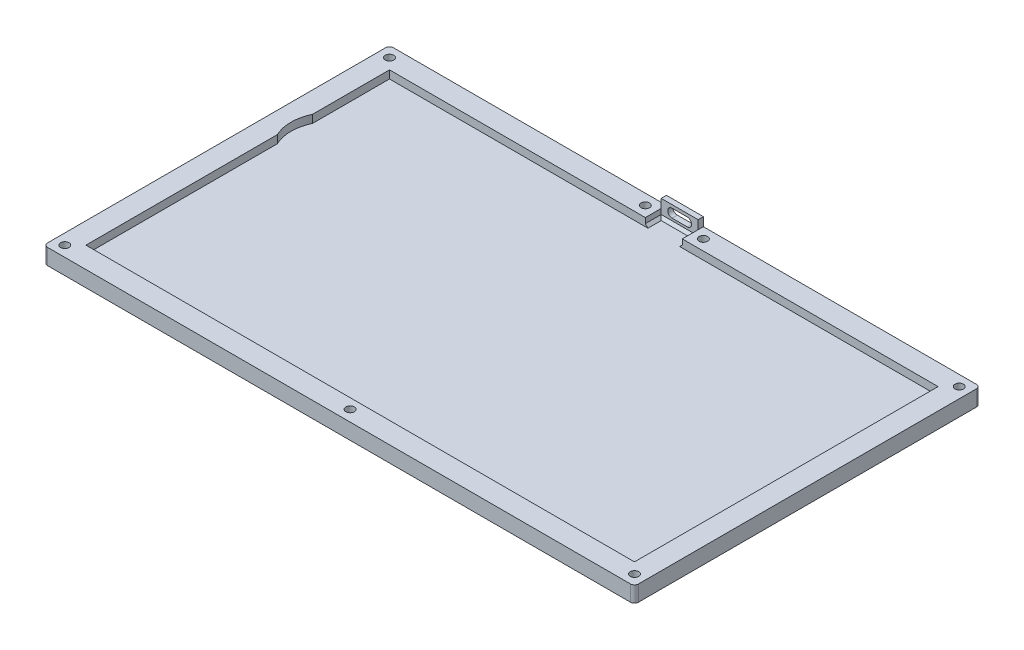
SolidWorks part; units mm, degrees
ref_plane "Front Plane" through (0, 0, 0) normal (0, 0, 1) x (1, 0, 0)
ref_plane "Top Plane" through (0, 0, 0) normal (0, 1, 0) x (1, 0, 0)
ref_plane "Right Plane" through (0, 0, 0) normal (1, 0, 0) x (0, 0, -1)
sketch "Sketch1" plane through (0, 0, 0) normal (0, 1, 0) x (1, 0, 0)
  line L1 (6.4113, 22.7059) -> (230.2097, 22.7059)
  line L2 (6.4113, 22.7059) -> (6.4113, 153.7054)
  line L3 (6.4113, 153.7054) -> (230.2097, 153.7054)
  line L4 (230.2097, 22.7059) -> (230.2097, 153.7054)
  line L6 (111.3105, 153.7054) -> (7.9113, 153.7054) construction
  line L7 (230.2097, 24.2059) -> (230.2097, 152.2054) construction
  line L8 (7.9113, 22.7059) -> (228.7097, 22.7059) construction
  line L9 (6.4113, 152.2054) -> (6.4113, 24.2059) construction
  point P9 (0, 0)
extrude "Boss-Extrude1" add sketch "Sketch1" along normal blind 3
sketch "Sketch2" plane through (0, 3, 0) normal (0, 1, 0) x (1, 0, 0)
  line L1 (14.4113, 30.7059) -> (222.2097, 30.7059)
  line L2 (14.4113, 30.7059) -> (14.4113, 145.7054)
  line L3 (14.4113, 145.7054) -> (222.2097, 145.7054)
  line L4 (222.2097, 30.7059) -> (222.2097, 145.7054)
  line L5 (230.2097, 153.7054) -> (6.4113, 153.7054)
  line L6 (230.2097, 153.7054) -> (230.2097, 22.7059)
  line L7 (230.2097, 22.7059) -> (6.4113, 22.7059)
  line L8 (6.4113, 153.7054) -> (6.4113, 22.7059)
  dimension "D1" = 8
  dimension "D2" = 8
  dimension "D3" = 8
  dimension "D4" = 8
extrude "Boss-Extrude2" add sketch "Sketch2" along normal blind 3
sketch "Sketch3" plane through (0, 6, 0) normal (0, 1, 0) x (1, 0, 0)
  line L0 (230.2097, 153.7054) -> (6.4113, 153.7054) construction
  line L1 (111.3105, 153.7054) -> (125.3105, 153.7054)
  line L2 (111.3105, 153.7054) -> (111.3105, 145.7054)
  line L3 (111.3105, 145.7054) -> (125.3105, 145.7054)
  line L4 (125.3105, 153.7054) -> (125.3105, 145.7054)
  line L5 (111.3105, 145.7054) -> (111.3105, 153.7054) construction
  line L6 (222.2097, 145.7054) -> (14.4113, 145.7054) construction
  line L7 (125.3105, 153.7054) -> (125.3105, 145.7054) construction
extrude "Boss-Extrude3" add sketch "Sketch3" along normal blind 3.3
sketch "Sketch7" plane through (0, 3, 0) normal (0, 1, 0) x (1, 0, 0)
  circle A0 centre (28.4113, 109.8975) radius 15.5
extrude "Cut-Extrude1" cut sketch "Sketch7" along normal up to next
hole_wizard "CSK for M3 SFHCS1" positions "Sketch5" profile "Sketch6" countersink size "M3" standard "ANSI Metric" end condition through all
sketch "Sketch5" plane through (0, 0, 0) normal (0, -1, 0) x (-1, 0, 0)
  point P0 (-10.4113, 26.7059)
  point P3 (-226.2097, 26.7059)
  point P6 (-226.2097, 149.7054)
  point P9 (-10.4113, 149.7054)
  point P13 (-118.3105, 26.8789)
  point P16 (-129.3105, 149.7054)
  point P19 (-107.3105, 149.7054)
sketch "Sketch6" plane through (10.4113, 0, -26.7059) normal (1, 0, 0) x (0, 0, -1)
  line L0 (0, 0) -> (0, 9.3)
  line L1 (0, 9.3) -> (1.6, 9.3)
  line L2 (1.6, 9.3) -> (1.6, 1.76)
  line L3 (1.6, 1.76) -> (3.36, 0)
  line L5 (3.36, 0) -> (0, 0)
  line L6 (-1.6, 1.76) -> (-3.36, 0) construction
  line L11 (0, -6.35) -> (0, 107.95) construction
  dimension "Thru Hole Dia." = 3.2
  dimension "Thru Hole Depth" = 9.3
  dimension "Near C'Sink Dia." = 6.72
  dimension "Near C'Sink Angle" = 90
fillet "Fillet1" radius 1.5 4 edges at (6.4113, 3, -153.7054) (6.4113, 3, -22.7059) (230.2097, 3, -153.7054) (230.2097, 3, -22.7059)
sketch "Sketch9" plane through (0, 0, -153.7054) normal (0, 0, -1) x (-1, 0, 0)
  line L0 (-121.1855, 6.4984) -> (-115.4355, 6.4984) construction
  line L1 (-121.1855, 8.1234) -> (-115.4355, 8.1234)
  line L2 (-121.1855, 4.8734) -> (-115.4355, 4.8734)
  line L3 (-118.3105, 6.4984) -> (-118.3105, 9.3) construction
  line L4 (-125.3105, 9.3) -> (-111.3105, 9.3) construction
  arc A0 (-121.1855, 8.1234) -> (-121.1855, 4.8734) centre (-121.1855, 6.4984) ccw
  arc A1 (-115.4355, 4.8734) -> (-115.4355, 8.1234) centre (-115.4355, 6.4984) ccw
  point P2 (-118.3105, 6.4984)
  point P7 (-122.8105, 6.4984)
  point P8 (-113.8105, 6.4984)
  point P13 (-118.3105, 6.4984)
  dimension "D1" = 9
  dimension "D2" = 3.25
extrude "Cut-Extrude2" cut sketch "Sketch9" against normal up to next
sketch "Sketch10" plane through (0, 0, -145.7054) normal (0, 0, 1) x (1, 0, 0)
  line L0 (222.2097, 3) -> (14.4113, 3) construction
  line L1 (125.3105, 9.3) -> (111.3105, 9.3)
  line L2 (125.3105, 9.3) -> (125.3105, 3)
  line L3 (125.3105, 3) -> (111.3105, 3)
  line L4 (111.3105, 9.3) -> (111.3105, 3)
  line L5 (111.3105, 9.3) -> (111.3105, 6) construction
extrude "Cut-Extrude3" cut sketch "Sketch10" against normal blind 6
chamfer "Chamfer1" distance 1 angle 45 3 edges at (125.3105, 3, -148.7054) (118.3105, 3, -151.7054) (111.3105, 3, -148.7054)
